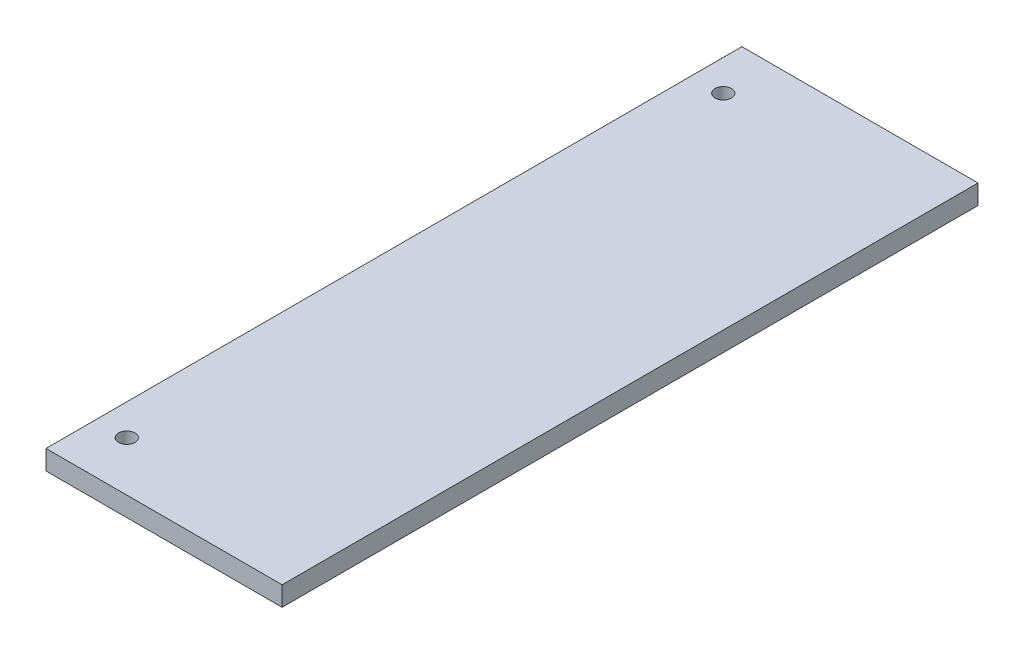
SolidWorks part; units mm, degrees
ref_plane "Front Plane" through (0, 0, 0) normal (0, 0, 1) x (1, 0, 0)
ref_plane "Top Plane" through (0, 0, 0) normal (0, 1, 0) x (1, 0, 0)
ref_plane "Right Plane" through (0, 0, 0) normal (1, 0, 0) x (0, 0, -1)
sketch "Sketch1" plane through (0, 0, 0) normal (0, 1, 0) x (1, 0, 0)
  line L1 (-15.0812, -44.45) -> (15.0813, -44.45)
  line L2 (-15.0812, -44.45) -> (-15.0812, 44.45)
  line L3 (-15.0812, 44.45) -> (15.0813, 44.45)
  line L4 (15.0813, -44.45) -> (15.0813, 44.45)
  line L5 (-15.0812, -44.45) -> (15.0813, 44.45) construction
  line L6 (-15.0812, 44.45) -> (15.0813, -44.45) construction
  point P0 (0, 0)
  dimension "D1" = 30.1625
  dimension "D2" = 88.9
extrude "Boss-Extrude1" add sketch "Sketch1" along normal blind 2.5
sketch "Sketch2" plane through (0, 2.5, 0) normal (0, 1, 0) x (1, 0, 0)
  line L0 (-11.1125, 38.1) -> (-11.1125, -38.1) construction
  circle A0 centre (-11.1125, 38.1) radius 1.05
  circle A1 centre (-11.1125, -38.1) radius 1.05
  point P5 (-11.1125, 0)
  dimension "D2" = 2.1
  dimension "D1" = 11.1125
  dimension "D3" = 76.2
extrude "Cut-Extrude1" cut sketch "Sketch2" against normal through all
